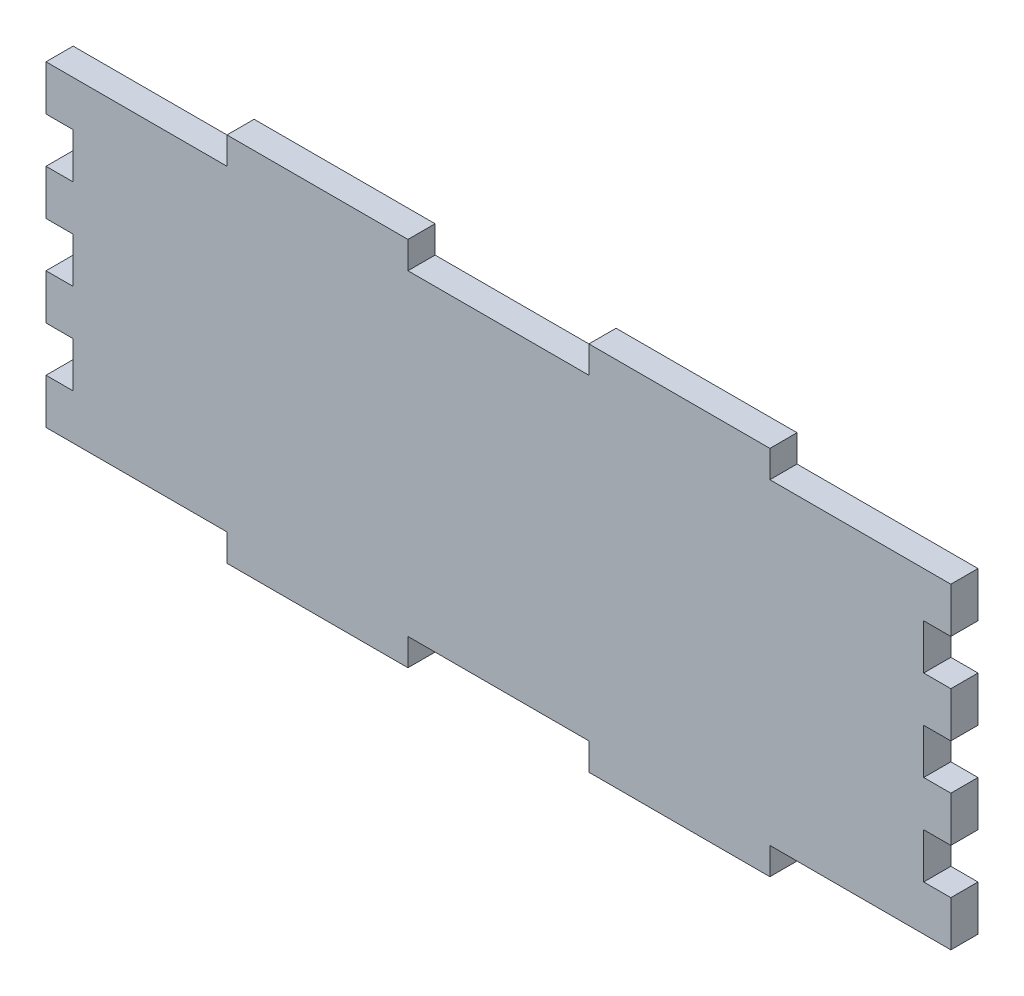
SolidWorks part; units mm, degrees
material "Pine"
ref_plane "Front Plane" through (0, 0, 0) normal (0, 0, 1) x (1, 0, 0)
ref_plane "Top Plane" through (0, 0, 0) normal (0, 1, 0) x (1, 0, 0)
ref_plane "Right Plane" through (0, 0, 0) normal (1, 0, 0) x (0, 0, -1)
sketch "Sketch1" plane through (0, 0, 0) normal (0, 0, 1) x (1, 0, 0)
  line L1 (-100, 41) -> (100, 41)
  line L2 (-100, 41) -> (-100, -41)
  line L3 (-100, -41) -> (100, -41)
  line L4 (100, 41) -> (100, -41)
  line L5 (-100, 41) -> (100, -41) construction
  line L6 (-100, -41) -> (100, 41) construction
  point P0 (0, 0)
  dimension "D1" = 82
  dimension "D2" = 200
extrude "Boss-Extrude1" add sketch "Sketch1" along normal blind 6
sketch "Sketch2" plane through (0, 0, 6) normal (0, 0, 1) x (1, 0, 0)
  line L0 (-20, -41) -> (-20, -35)
  line L1 (-100, -41) -> (-60, -41)
  line L2 (-100, -41) -> (-100, -35)
  line L3 (-100, -35) -> (-60, -35)
  line L4 (-60, -41) -> (-60, -35)
  line L5 (-20, -41) -> (20, -41)
  line L6 (20, -41) -> (20, -35)
  line L7 (-20, -35) -> (20, -35)
  line L8 (60, -41) -> (60, -35)
  line L9 (60, -41) -> (100, -41)
  line L10 (100, -41) -> (100, -35)
  line L11 (60, -35) -> (100, -35)
  dimension "D1" = 40
  dimension "D2" = 6
  dimension "D3" = 3
extrude "Cut-Extrude1" cut sketch "Sketch2" against normal blind 6
sketch "Sketch3" plane through (0, 0, 6) normal (0, 0, 1) x (1, 0, 0)
  line L0 (-100, 41) -> (-100, -35) construction
  line L1 (-100, -25) -> (-94, -25)
  line L2 (-100, -25) -> (-100, -15)
  line L3 (-100, -15) -> (-94, -15)
  line L4 (-94, -25) -> (-94, -15)
  line L5 (-60, -35) -> (-100, -35) construction
  line L10 (-100, -5) -> (-100, 5)
  line L11 (-100, -5) -> (-94, -5)
  line L12 (-94, -5) -> (-94, 5)
  line L13 (-100, 5) -> (-94, 5)
  line L18 (-100, 15) -> (-100, 25)
  line L19 (-100, 15) -> (-94, 15)
  line L20 (-94, 15) -> (-94, 25)
  line L21 (-100, 25) -> (-94, 25)
  dimension "D1" = 10
  dimension "D2" = 10
  dimension "D3" = 6
  dimension "D4" = 1
  dimension "D5" = 3
extrude "Cut-Extrude2" cut sketch "Sketch3" against normal blind 10
mirror "Mirror1" about plane through (0, 0, 0) normal (1, 0, 0) of "Cut-Extrude2"
mirror "Mirror2" about plane through (0, 0, 0) normal (0, 1, 0) of "Cut-Extrude1"
